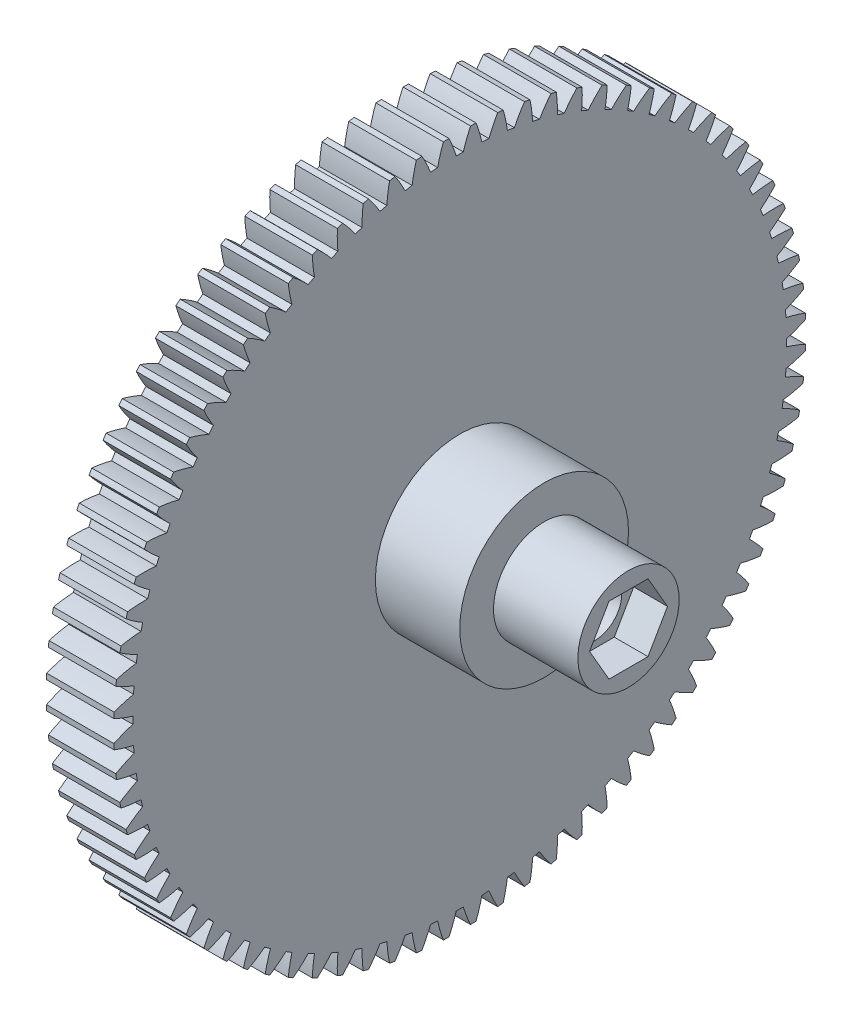
SolidWorks part; units mm, degrees
ref_plane "Plane1" through (0, 0, 0) normal (0, 0, 1) x (1, 0, 0)
ref_plane "Plane2" through (0, 0, 0) normal (0, 1, 0) x (1, 0, 0)
ref_plane "Plane3" through (0, 0, 0) normal (1, 0, 0) x (0, 0, -1)
sketch "HoldingSke" plane through (0, 0, 0) normal (0, 1, 0) x (1, 0, 0)
  line L0 (0, 0) -> (0.1736, -0.9848)
  line L1 (-15, 0) -> (100, 0) construction
  line L2 (0, 0) -> (-2.1039, 2.3779)
  line L3 (0, 0) -> (-11.863, 4.5341)
  line L4 (0, 0) -> (1.4996, 8.5048)
  line L5 (0, 0) -> (-46.8476, -17.4728)
  line L6 (0, 0) -> (-6.6317, -4.4744)
  line L7 (-2.1039, 2.3779) -> (8.6586, 51.2059)
  line L8 (-76.2, 54.61) -> (-74.4, 54.61)
  line L9 (-71.009, 38.7566) -> (-53.1078, 45.2721)
  line L10 (-76.2, 71.12) -> (104.1128, 71.12)
  line L11 (0, 0) -> (-8, 0)
  line L12 (-76.2, 101.6) -> (-76.162, 101.6)
  line L13 (24.9733, 27.94) -> (52.9518, 28.4284)
  line L14 (24.9733, 27.94) -> (24.9743, 27.94)
  line L15 (24.9733, 27.94) -> (100.4006, 29.5858)
  line L16 (-63.627, -1) -> (-12.827, -1)
  circle A0 centre (0, 0) radius 5
  circle A1 centre (0, 0) radius 37.5
  circle A2 centre (0, 0) radius 37.5
  circle A3 centre (0, 0) radius 5
  dimension "MHD" = 75
  dimension "Hub_dia" = 75
  dimension "Bore" = 10
  dimension "MBD" = 10
  dimension "Num_teeth" = 80
  dimension "Pitch" = 1
  dimension "Overall_len" = 50
  dimension "Show_teeth" = 80
  dimension "Thickness" = 8
  dimension "OAL" = 50.0001
  dimension "T_dim" = 1.8
  dimension "Ap" = 20
  dimension "H" = 19.05
  dimension "Pitch_radius" = 180.3128
  dimension "Width" = 8
  dimension "Backlash" = 0.038
  dimension "Addendum_fac" = 1
  dimension "Dedendum_fac" = 1.25
  dimension "Clearance_fac" = 0.25
  dimension "Dedendum_add" = 0.001
  dimension "Module" = 1
sketch "BasProSke" plane through (0, 0, 0) normal (0, 1, 0) x (1, 0, 0)
  line L0 (-10, 0) -> (60, 0) construction
  line L1 (0, 0) -> (0, 41)
  line L2 (0, 0) -> (8, 0)
  line L3 (8, 0) -> (8, 41)
  line L4 (8, 41) -> (0, 41)
  dimension "Thickness" = 8
  dimension "Diameter" = 82
revolve "Base-Revolve" add sketch "BasProSke" angle 360 about L0
sketch "TooCutSke" plane through (0, 0, 0) normal (1, 0, 0) x (0, 0, -1)
  line L1 (0, 0) -> (0, 107) construction
  line L2 (0, 0) -> (-0.8518, 39.9909) construction
  line L3 (0, 0) -> (-3.1403, 79.9254) construction
  line L4 (-0.8518, 39.9909) -> (-1.5701, 39.9627) construction
  arc A0 (0.4206, 38.7467) -> (-0.4206, 38.7467) centre (0, 0) ccw
  arc A1 (1.2919, 41.0051) -> (-1.2919, 41.0051) centre (0, 0) ccw
  circle A2 centre (0, 0) radius 40 construction
  circle A3 centre (0, 0) radius 37.5877 construction
  arc A4 (-0.4206, 38.7467) -> (-1.2919, 41.0051) centre (-15.7409, 34.133) ccw
  arc A5 (1.2919, 41.0051) -> (0.4206, 38.7467) centre (15.7409, 34.133) ccw
  dimension "Root_dia" = 77.498
  dimension "Overcut_dia" = 82.0508
  dimension "Pitch_dia" = 80
  dimension "Base_dia" = 75.1754
  dimension "Flank_rad" = 16
  dimension "Half_ang" = 2.25
  dimension "Half_CT" = 0.7188
extrude "ToothCut" cut sketch "TooCutSke" along normal through all
fillet "Breaks" [suppressed] radius 0.02 tangent propagation no
fillet "RootFillets" [suppressed] radius 0.251
pattern_circular "TeethCuts" count 80 every 4.5 about axis through (-10, 0, 0) along (1, 0, 0) of "ToothCut", "RootFillets", "Breaks"
sketch "HubNeaOneSke" plane through (0, 0, 0) normal (-1, 0, 0) x (0, 0, 1)
  circle A0 centre (0, 0) radius 37.5
  dimension "Diameter" = 75
extrude "HubNearOne" [suppressed] add sketch "HubNeaOneSke" along normal blind 42.0001
sketch "HubNeaBotSke" plane through (0, 0, 0) normal (-1, 0, 0) x (0, 0, 1)
  circle A0 centre (0, 0) radius 37.5
  dimension "Diameter" = 75
extrude "HubNearBoth" [suppressed] add sketch "HubNeaBotSke" along normal blind 21
ref_plane "FarPln" through (8, 0, 0) normal (1, 0, 0) x (0, 0, -1)
sketch "HubFarSke" plane through (8, 0, 0) normal (1, 0, 0) x (0, 0, -1)
  circle A0 centre (0, 0) radius 37.5
  dimension "Diameter" = 75
extrude "HubFar" [suppressed] add sketch "HubFarSke" along normal blind 21
sketch "BorSke" plane through (0, 0, 0) normal (1, 0, 0) x (0, 0, -1)
  circle A0 centre (0, 0) radius 5
  dimension "Diameter" = 10
extrude "Bore" cut sketch "BorSke" along normal mid plane 100.0001
sketch "KeySke" plane through (0, 0, 0) normal (1, 0, 0) x (0, 0, -1)
  line L0 (-2, 0) -> (-2, 6.8)
  line L1 (-2, 6.8) -> (2, 6.8)
  line L2 (2, 6.8) -> (2, 0)
  line L3 (0, 0) -> (0, 34) construction
  line L4 (-2, 0) -> (2, 0)
  dimension "Offset" = 6.8
  dimension "Width" = 4
extrude "Keyway" [suppressed] cut sketch "KeySke" along normal mid plane 100.0001
pattern_circular "Keyway2" [suppressed] count 2 every 90 about axis through (-10, 0, 0) along (1, 0, 0) reverse direction yes
sketch "Esboço1" plane through (8, 0, 0) normal (1, 0, 0) x (0, 0, -1)
  circle A0 centre (0, 0) radius 10
extrude "Ressalto-extrusão1" add sketch "Esboço1" along normal blind 10
sketch "Esboço2" plane through (18, 0, 0) normal (1, 0, 0) x (0, 0, -1)
  circle A0 centre (0, 0) radius 6
extrude "Ressalto-extrusão2" add sketch "Esboço2" along normal blind 10
sketch "Esboço3" plane through (28, 0, 0) normal (1, 0, 0) x (0, 0, -1)
  line L0 (0, 6) -> (0, -6) construction
  line L2 (-4.6188, 0) -> (-2.3094, -4)
  line L3 (-2.3094, -4) -> (2.3094, -4)
  line L4 (2.3094, -4) -> (4.6188, 0)
  line L5 (4.6188, 0) -> (2.3094, 4)
  line L6 (2.3094, 4) -> (-2.3094, 4)
  line L7 (-2.3094, 4) -> (-4.6188, 0)
  circle A0 centre (0, 0) radius 6 construction
  circle A1 centre (0, 0) radius 6 construction
  circle A2 centre (0, 0) radius 4 construction
  dimension "D1" = 8
extrude "Corte-extrusão1" cut sketch "Esboço3" against normal blind 4
sketch "Esboço4" plane through (8, 0, 0) normal (-1, 0, 0) x (0, 0, 1)
  circle A0 centre (0, 0) radius 5
extrude "Ressalto-extrusão3" add sketch "Esboço4" along normal up to surface (8 mm away) up to face at (0, 0, -5)
sketch "Esboço5" plane through (24, 0, 0) normal (1, 0, 0) x (0, 0, -1)
  circle A0 centre (0, 0) radius 3.2
extrude "Corte-extrusão2" cut sketch "Esboço5" against normal through all
fillet "Filete1" radius 20 1 edges at (0, 0, -3.2)
equation "' \"Module@HoldingSke\" = 6.35"
equation "' \"Num_teeth@HoldingSke\" = 12"
equation "' \"Ap@HoldingSke\" =  20"
equation "' \"Ap@HoldingSke\" = 20"
equation "' \"Width@HoldingSke\" = 0.5 * 25.4"
equation "' \"Hub_dia@HoldingSke\"= 1 * 25.4"
equation "' \"Hub_dia@HoldingSke\" = 1 * 25.4"
equation "' \"Overall_len@HoldingSke\" = 1.0 * 25.4"
equation "' \"Bore@HoldingSke\" = 0.75 * 25.4"
equation "' \"T_dim@HoldingSke\" = 0.1 * 25.4"
equation "' \"Width@KeySke\" = 0.25 * 25.4"
equation "' \"Show_teeth@HoldingSke\" = 13"
equation "' \"Backlash@HoldingSke\" = 0.009 * 25.4"
equation "' \"Addendum_fac@HoldingSke\" = 1.0"
equation "' \"Dedendum_fac@HoldingSke\" = 1.25"
equation "' \"Dedendum_add@HoldingSke\" = 0.00005 * 25.4"
equation "' \"Clearance_fac@HoldingSke\" = 0.25"
equation "\"Pitch@HoldingSke\" = 1 / \"Module@HoldingSke\""
equation "\"Overcut_dia@TooCutSke\" = (\"Num_teeth@HoldingSke\" + 2 * \"Addendum_fac@HoldingSke\") / \"Pitch@HoldingSke\" + 0.002 * 25.4"
equation "\"Pitch_dia@TooCutSke\" = \"Num_teeth@HoldingSke\" / \"Pitch@HoldingSke\""
equation "\"Base_dia@TooCutSke\" = \"Num_teeth@HoldingSke\" / \"Pitch@HoldingSke\" * cos((\"Ap@HoldingSke\"  * 3.14159265 / 180))"
equation "\"Root_dia@TooCutSke\" = (\"Num_teeth@HoldingSke\" + 2) / \"Pitch@HoldingSke\" - 2 * (\"Addendum_fac@HoldingSke\" + \"Dedendum_fac@HoldingSke\") / \"Pitch@HoldingSke\" - \"Dedendum_add@HoldingSke\" * 2"
equation "\"Half_ang@TooCutSke\" = 180 / \"Num_teeth@HoldingSke\""
equation "\"Half_CT@TooCutSke\" = \"Num_teeth@HoldingSke\" / \"Pitch@HoldingSke\" * sin((3.14159265 / 2 / \"Num_teeth@HoldingSke\")) / 2 - 7 * \"Backlash@HoldingSke\" / 4"
equation "\"Flank_rad@TooCutSke\" = \"Num_teeth@HoldingSke\" / \"Pitch@HoldingSke\" / 5"
equation "\"Radius@RootFillets\" = \"Clearance_fac@HoldingSke\" / \"Pitch@HoldingSke\" + \"Dedendum_add@HoldingSke\""
equation "\"Break_rad@Breaks\" = 0.02 / \"Pitch@HoldingSke\""
equation "\"Thickness@HoldingSke\" = \"Width@HoldingSke\""
equation "\"OAL@HoldingSke\" = \"Thickness@HoldingSke\""
equation "\"MHD@HoldingSke\" = (\"Num_teeth@HoldingSke\" + 2) / \"Pitch@HoldingSke\" - 2 * (\"Addendum_fac@HoldingSke\" + \"Dedendum_fac@HoldingSke\")  / \"Pitch@HoldingSke\" - \"Dedendum_add@HoldingSke\" * 2"
equation "\"MBD@HoldingSke\" = (\"Num_teeth@HoldingSke\" + 2) / \"Pitch@HoldingSke\" - 2 * (\"Addendum_fac@HoldingSke\" + \"Dedendum_fac@HoldingSke\")  / \"Pitch@HoldingSke\" - \"Dedendum_add@HoldingSke\" * 2 - 0.002 * 25.4"
equation "\"MHD@HoldingSke\" = ((sgn( \"MHD@HoldingSke\" - \"Hub_dia@HoldingSke\" )-1)*( \"MHD@HoldingSke\" - \"Hub_dia@HoldingSke\" ))/-2+ \"Hub_dia@HoldingSke\""
equation "\"MBD@HoldingSke\" = ((sgn( \"MBD@HoldingSke\" - \"Bore@HoldingSke\" )-1)*( \"MBD@HoldingSke\" - \"Bore@HoldingSke\" ))/-2+ \"Bore@HoldingSke\""
equation "\"OAL@HoldingSke\" = ((sgn( \"OAL@HoldingSke\" - \"Overall_len@HoldingSke\" )+1)*( \"OAL@HoldingSke\" - \"Overall_len@HoldingSke\" ))/2 + \"Overall_len@HoldingSke\" + 0.000002 * 25.4"
equation "\"Num_teeth@TeethCuts\" = int( \"Show_teeth@HoldingSke\" ) + 1"
equation "\"Num_teeth@TeethCuts\" = ((sgn( \"Num_teeth@TeethCuts\" - \"Num_teeth@HoldingSke\" )-1)*( \"Num_teeth@TeethCuts\" - \"Num_teeth@HoldingSke\" ))/-2+ \"Num_teeth@HoldingSke\""
equation "\"Num_teeth@TeethCuts\" = ((sgn( \"Num_teeth@TeethCuts\" - 2.0)+1)*( \"Num_teeth@TeethCuts\" - 2.0))/2 +2.0"
equation "\"Angle@TeethCuts\" = 360.0 / \"Num_teeth@HoldingSke\""
equation "\"Diameter@BasProSke\" = (\"Num_teeth@HoldingSke\" + 2 * \"Addendum_fac@HoldingSke\") / \"Pitch@HoldingSke\""
equation "\"Thickness@BasProSke\"  = \"Thickness@HoldingSke\""
equation "' \"Fillet_rad@BasProSke\" =  \"Thickness@HoldingSke\" * 0.05"
equation "' \"Fillet_rad@BasProSke\" = \"Thickness@HoldingSke\" * 0.05"
equation "\"MHD@HoldingSke\" = ((sgn( \"MHD@HoldingSke\" - \"Root_dia@TooCutSke\" )-1)*( \"MHD@HoldingSke\" - \"Root_dia@TooCutSke\" ))/-2+ \"Root_dia@TooCutSke\""
equation "\"Diameter@HubNeaOneSke\" = \"MHD@HoldingSke\""
equation "\"Length@HubNearOne\" = \"OAL@HoldingSke\" - \"Thickness@BasProSke\""
equation "\"Diameter@HubNeaBotSke\" = \"MHD@HoldingSke\""
equation "\"Length@HubNearBoth\" = ( \"OAL@HoldingSke\" - \"Thickness@BasProSke\" ) / 2.0"
equation "\"Thickness@FarPln\" = \"Thickness@BasProSke\""
equation "\"Diameter@HubFarSke\" = \"MHD@HoldingSke\""
equation "\"Length@HubFar\" = ( \"OAL@HoldingSke\" - \"Thickness@BasProSke\" ) / 2.0"
equation "\"Diameter@BorSke\" = \"MBD@HoldingSke\""
equation "\"D1@Bore\" = \"OAL@HoldingSke\" * 2.0"
equation "\"D1@Keyway\" = \"OAL@HoldingSke\" * 2.0"
equation "\"Offset@KeySke\" = \"T_dim@HoldingSke\" + \"MBD@HoldingSke\" / 2.0"
